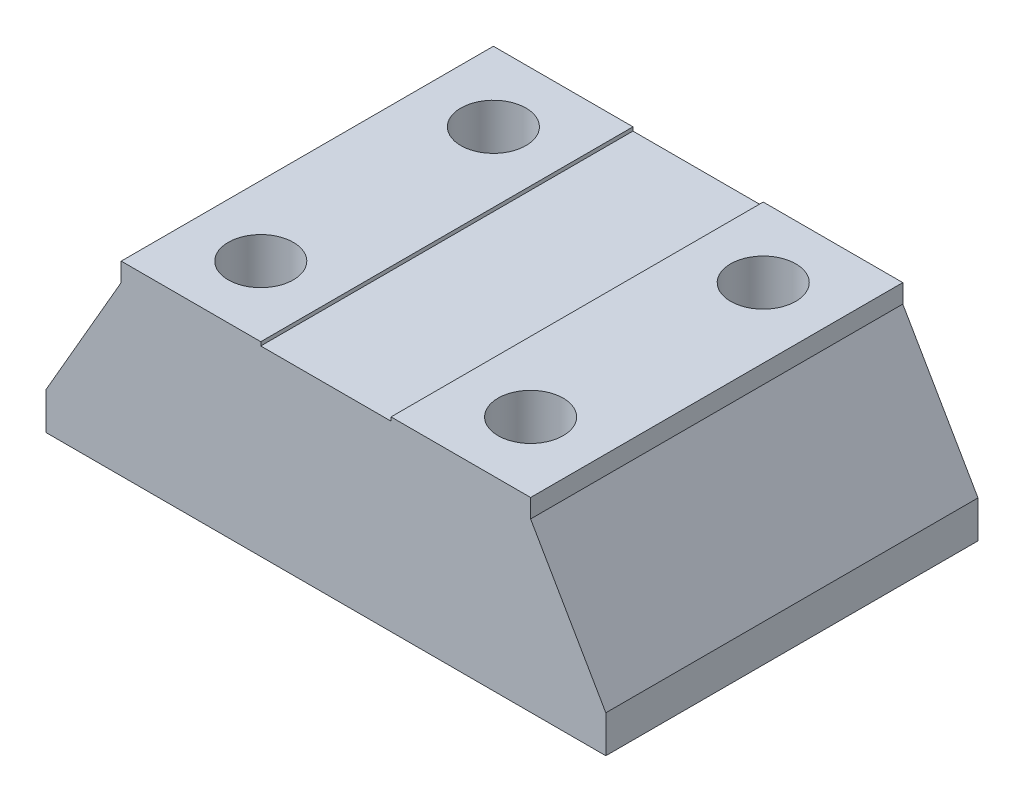
SolidWorks part; units mm, degrees
ref_plane "Piano frontale" through (0, 0, 0) normal (0, 0, 1) x (1, 0, 0)
ref_plane "Piano superiore" through (0, 0, 0) normal (0, 1, 0) x (1, 0, 0)
ref_plane "Piano destro" through (0, 0, 0) normal (1, 0, 0) x (0, 0, -1)
sketch "Schizzo1" plane through (0, 0, 0) normal (0, 0, 1) x (1, 0, 0)
  line L0 (0, 10) -> (0, 0) construction
  line L1 (11, 9) -> (11, 10)
  line L2 (-11, 10) -> (11, 10)
  line L3 (11, 9) -> (15.0415, 2)
  line L4 (15.0415, 2) -> (15.0415, 0)
  line L5 (-15.0415, 0) -> (15.0415, 0)
  line L6 (-15.0415, 2) -> (-15.0415, 0)
  line L7 (-11, 9) -> (-15.0415, 2)
  line L8 (-11, 9) -> (-11, 10)
  point P16 (0, 9.6)
  dimension "D1" = 150
  dimension "D2" = 2
  dimension "D3" = 1
  dimension "D4" = 11
  dimension "D5" = 10
extrude "Estrusione-Estrusione1" add sketch "Schizzo1" along normal mid plane 20
sketch "Schizzo2" plane through (0, 10, 0) normal (0, 1, 0) x (1, 0, 0)
  line L0 (11, -10) -> (11, 10) construction
  line L1 (-7.25, -6.25) -> (7.25, -6.25) construction
  line L2 (-7.25, -6.25) -> (-7.25, 6.25) construction
  line L3 (-7.25, 6.25) -> (7.25, 6.25) construction
  line L4 (7.25, -6.25) -> (7.25, 6.25) construction
  line L5 (-7.25, -6.25) -> (7.25, 6.25) construction
  line L6 (-7.25, 6.25) -> (7.25, -6.25) construction
  line L8 (11, 10) -> (-11, 10) construction
  circle A0 centre (7.25, 6.25) radius 1.75
  circle A1 centre (-7.25, 6.25) radius 1.75
  circle A2 centre (-7.25, -6.25) radius 1.75
  circle A3 centre (7.25, -6.25) radius 1.75
  point P0 (0, 0)
  dimension "D3" = 3.5
  dimension "D1" = 3.75
  dimension "D2" = 3.75
extrude "Taglio-Estrusione1" cut sketch "Schizzo2" against normal through all
sketch "Schizzo3" plane through (0, 10, 0) normal (0, 1, 0) x (1, 0, 0)
  line L0 (11, 10) -> (-11, 10) construction
  line L1 (3.5, -10) -> (-3.5, -10)
  line L2 (3.5, -10) -> (3.5, 10)
  line L3 (3.5, 10) -> (-3.5, 10)
  line L4 (-3.5, -10) -> (-3.5, 10)
  line L5 (3.5, -10) -> (-3.5, 10) construction
  line L6 (3.5, 10) -> (-3.5, -10) construction
  point P0 (0, 0)
  line M7 (11, 10) -> (-11, 10)
  line M9 (-11, -10) -> (11, -10)
  dimension "D1" = 7
extrude "Taglio-Estrusione2" cut sketch "Schizzo3" against normal blind 0.2 contours L4 L2 M9 M7 region at (0, 10, 0)
